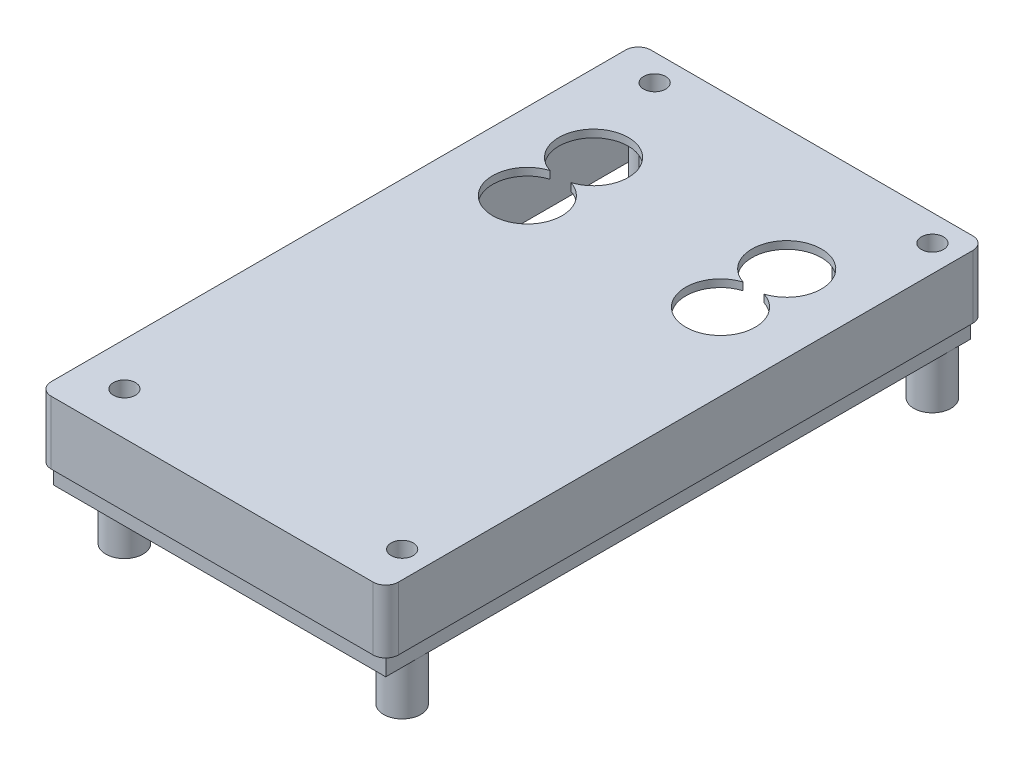
SolidWorks part; units mm, degrees
ref_plane "Front Plane" through (0, 0, 0) normal (0, 0, 1) x (1, 0, 0)
ref_plane "Top Plane" through (0, 0, 0) normal (0, 1, 0) x (1, 0, 0)
ref_plane "Right Plane" through (0, 0, 0) normal (1, 0, 0) x (0, 0, -1)
sketch "Sketch1" plane through (0, 0, 0) normal (0, 1, 0) x (1, 0, 0)
  line L1 (0, 0) -> (55, 0)
  line L2 (0, 0) -> (0, -95)
  line L3 (0, -95) -> (55, -95)
  line L4 (55, 0) -> (55, -95)
  dimension "D1" = 95
  dimension "D2" = 55
extrude "Boss-Extrude1" add sketch "Sketch1" against normal blind 10 contours L2 L3 L4 L1
sketch "Sketch3" plane through (0, -10, 0) normal (0, -1, 0) x (1, 0, 0)
  line L0 (0, 0) -> (0, 95) construction
  line L1 (1.2, 93.8) -> (53.8, 93.8)
  line L2 (1.2, 93.8) -> (1.2, 1.2)
  line L3 (1.2, 1.2) -> (53.8, 1.2)
  line L4 (53.8, 93.8) -> (53.8, 1.2)
  line L5 (0, 95) -> (55, 95) construction
  line L6 (55, 0) -> (55, 95) construction
  line L7 (0, 0) -> (55, 0) construction
  dimension "D1" = 1.2
  dimension "D2" = 1.2
  dimension "D3" = 1.2
  dimension "D4" = 1.2
extrude "Cut-Extrude1" cut sketch "Sketch3" against normal offset from surface (8.8 mm away) 1.2 up to face at (27.5, 0, 47.5)
fillet "Fillet1" radius 2 4 edges at (55, -5, 95) (55, -5, 0) (0, -5, 0) (0, -5, 95)
sketch "Sketch4" plane through (0, 0, 0) normal (0, 1, 0) x (1, 0, 0)
  circle A0 centre (42.8, -29.77) radius 5.5
  circle A1 centre (42.8, -19.28) radius 5.5
  arc A2 (43.0291, -24.525) -> (42.5709, -24.525) centre (42.8, -19.28) ccw construction
  arc A3 (42.5709, -24.525) -> (43.0291, -24.525) centre (42.8, -29.77) ccw construction
  dimension "D1" = 11
  dimension "D2" = 11
extrude "Cut-Extrude2" cut sketch "Sketch4" against normal up to next contours A0 | A1
sketch "Sketch5" plane through (0, 0, 0) normal (0, 1, 0) x (1, 0, 0)
  circle A0 centre (12.2, -29.77) radius 5.5
  circle A1 centre (12.2, -19.28) radius 5.5
  arc A2 (11.9709, -24.525) -> (12.4291, -24.525) centre (12.2, -29.77) ccw construction
  arc A3 (12.4291, -24.525) -> (11.9709, -24.525) centre (12.2, -19.28) ccw construction
  dimension "D1" = 11
  dimension "D2" = 11
extrude "Cut-Extrude3" cut sketch "Sketch5" against normal up to next contours A1 | A0
ref_axis "Axis1" through (12.2, -1.2, 13.78) along (0, 0, 1)
sketch "Sketch7" plane through (0, -1.2, 0) normal (0, -1, 0) x (1, 0, 0)
  circle A0 centre (50.8, 88.2) radius 2.95
  arc A1 (53.8, 90.0028) -> (53.8, 86.3972) centre (50.8, 88.2) ccw construction
  circle A2 centre (6.8, 88.2) radius 2.95
  circle A3 centre (6.8, 4.2) radius 2.95
  circle A4 centre (50.8, 4.2) radius 2.95
  dimension "D3" = 5.9
  dimension "D4" = 37.6553
  dimension "D5" = 20.325
  dimension "D1" = 2
  dimension "D2" = 2
extrude "Boss-Extrude4" add sketch "Sketch7" along normal blind 20
sketch "Sketch8" plane through (0, 0, 0) normal (0, 1, 0) x (1, 0, 0)
  circle A0 centre (6.8, -88.2) radius 1.75
  circle A1 centre (6.8, -88.2) radius 2.95 construction
  circle A2 centre (50.8, -88.2) radius 1.75
  circle A3 centre (50.8, -4.2) radius 1.75
  circle A4 centre (6.8, -4.2) radius 1.75
  circle A5 centre (50.8, -88.2) radius 2.95 construction
  circle A6 centre (6.8, -4.2) radius 2.95 construction
  dimension "D3" = 3.5
  dimension "D1" = 2
  dimension "D2" = 2
extrude "Cut-Extrude4" cut sketch "Sketch8" against normal up to next
sketch "Sketch10" plane through (0, -1.2, 0) normal (0, -1, 0) x (1, 0, 0)
  line L0 (1.2, 93.8) -> (1.2, 1.2)
  line L1 (1.2, 1.2) -> (16.2, 1.2)
  line L2 (53.8, 1.2) -> (1.2, 1.2) construction
  line L3 (16.2, 1.2) -> (16.2, 2.4)
  line L4 (16.2, 2.4) -> (2.4, 2.4)
  line L5 (2.4, 2.4) -> (2.4, 92.6)
  line L6 (2.4, 92.6) -> (52.6, 92.6)
  line L7 (52.6, 92.6) -> (52.6, 2.4)
  line L8 (52.6, 2.4) -> (38.8, 2.4)
  line L9 (38.8, 2.4) -> (38.8, 1.2)
  line L10 (38.8, 1.2) -> (53.8, 1.2)
  line L11 (53.8, 1.2) -> (53.8, 93.8)
  line L12 (53.8, 93.8) -> (1.2, 93.8)
  dimension "D1" = 1.2
  dimension "D2" = 1.2
  dimension "D3" = 1.2
  dimension "D4" = 1.2
  dimension "D5" = 15
  dimension "D6" = 15
  dimension "D7" = 1.2
extrude "Boss-Extrude5" add sketch "Sketch10" along normal blind 12
sketch "Sketch11" plane through (0, -1.2, 0) normal (0, -1, 0) x (1, 0, 0)
  circle A0 centre (12.2, 9.275) radius 2
  circle A1 centre (12.2, 9.275) radius 1.1 construction
  circle A3 centre (42.8, 9.275) radius 2
  circle A4 centre (12.2, 39.775) radius 2
  circle A5 centre (42.8, 39.775) radius 2
  arc A6 (40.55, 9.275) -> (45.05, 9.275) centre (42.8, 9.275) ccw construction
  arc A8 (14.45, 39.775) -> (9.95, 39.775) centre (12.2, 39.775) ccw construction
  arc A9 (45.05, 39.775) -> (40.55, 39.775) centre (42.8, 39.775) ccw construction
  dimension "D1" = 4
extrude "Boss-Extrude6" add sketch "Sketch11" along normal blind 10 contours A5 | A4 | A0 | A3
sketch "Sketch12" plane through (0, -11.2, 0) normal (0, -1, 0) x (-1, 0, 0)
  circle A0 centre (-42.8, -39.775) radius 0.75
  circle A1 centre (-12.2, -39.775) radius 0.75
  circle A2 centre (-42.8, -9.275) radius 0.75
  circle A3 centre (-12.2, -9.275) radius 0.75
  circle A4 centre (-42.8, -39.775) radius 2 construction
  circle A5 centre (-12.2, -39.775) radius 2 construction
  circle A6 centre (-42.8, -9.275) radius 2 construction
  circle A7 centre (-12.2, -9.275) radius 2 construction
  dimension "D1" = 1.5
extrude "Cut-Extrude5" cut sketch "Sketch12" against normal blind 7
